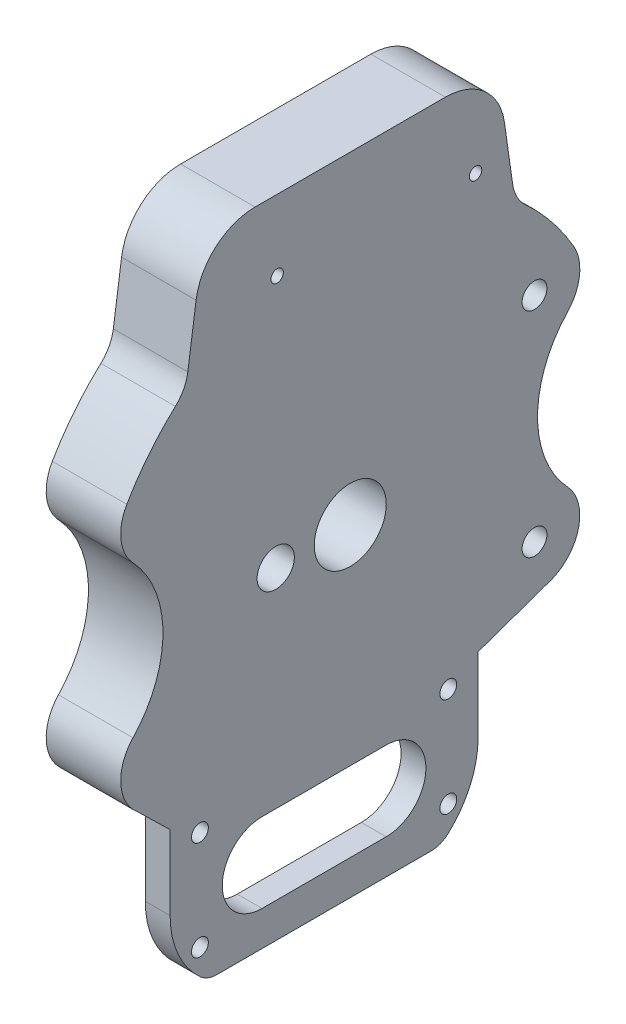
SolidWorks part; units mm, degrees
ref_plane "Płaszczyzna przednia" through (0, 0, 0) normal (0, 0, 1) x (1, 0, 0)
ref_plane "Płaszczyzna górna" through (0, 0, 0) normal (0, 1, 0) x (1, 0, 0)
ref_plane "Płaszczyzna prawa" through (0, 0, 0) normal (1, 0, 0) x (0, 0, -1)
sketch "Szkic1" plane through (0, 0, 0) normal (1, 0, 0) x (0, 0, -1)
  line L5 (0, 0) -> (0, 195.8303) construction
  line L42 (14.4695, -100) -> (-35.5305, -100) construction
  line L44 (14.4695, -84) -> (-35.5305, -84)
  line L45 (14.4695, -116) -> (-35.5305, -116)
  line L46 (30.5104, 100) -> (-9.4896, 100) construction
  line L47 (30.5104, 105) -> (-9.4896, 105) construction
  line L48 (30.5104, 95) -> (-9.4896, 95) construction
  line L49 (-10.5305, -100) -> (-10.5305, -46.7527) construction
  line L50 (-13.6636, -130) -> (20.5826, 195.8303) construction
  line L51 (0, 0) -> (120, 0) construction
  line L52 (0, 0) -> (0, -130.3815) construction
  line L53 (-72.5305, -70) -> (-85.8486, -57.0401)
  line L54 (-72.5305, -100) -> (-72.5305, -70)
  line L55 (51.4695, -70) -> (81.2407, -59.5241)
  line L56 (-35.5305, -130) -> (-53.6689, -130)
  line L57 (51.4695, -100) -> (51.4695, -70)
  line L58 (14.4695, -130) -> (32.6078, -130)
  line L59 (14.4695, -130) -> (-35.5305, -130)
  line L60 (62.0766, 109.386) -> (65.4007, 86.06)
  line L61 (-38.3166, 130) -> (38.3166, 130)
  line L62 (-62.0766, 109.386) -> (-65.4007, 86.06)
  circle A0 centre (0, 0) radius 14.5
  circle A3 centre (0, 0) radius 85.75 construction
  arc A56 (14.4695, -84) -> (14.4695, -116) centre (14.4695, -100) cw
  arc A57 (-35.5305, -116) -> (-35.5305, -84) centre (-35.5305, -100) cw
  arc A60 (30.5104, 105) -> (30.5104, 95) centre (30.5104, 100) cw construction
  arc A61 (-9.4896, 95) -> (-9.4896, 105) centre (-9.4896, 100) cw construction
  arc A62 (32.6078, -130) -> (39.3257, -127.4074) centre (32.6078, -120) ccw
  arc A63 (-60.3868, -127.4074) -> (-53.6689, -130) centre (-53.6689, -120) ccw
  arc A65 (51.4695, -100) -> (39.3257, -127.4074) centre (14.4695, -100) cw
  arc A66 (-60.3868, -127.4074) -> (-72.5305, -100) centre (-35.5305, -100) cw
  arc A67 (87.4958, -30.51) -> (81.2407, -59.5241) centre (74.4106, -42.8703) cw
  arc A68 (87.4958, -30.51) -> (87.4958, 30.51) centre (120, 0) cw
  arc A69 (89.9789, 52.1516) -> (87.4958, 30.51) centre (74.1894, 43) cw
  arc A70 (70.4086, 76.5417) -> (89.9789, 52.1516) centre (0, 0) cw
  arc A71 (65.4007, 86.06) -> (70.4086, 76.5417) centre (81.2407, 88.3174) ccw
  arc A72 (38.3166, 130) -> (62.0766, 109.386) centre (38.3166, 106) cw
  arc A73 (-38.3166, 130) -> (-62.0766, 109.386) centre (-38.3166, 106) ccw
  arc A74 (-65.4007, 86.06) -> (-70.4086, 76.5417) centre (-81.2407, 88.3174) cw
  arc A75 (-70.4086, 76.5417) -> (-89.9789, 52.1516) centre (0, 0) ccw
  arc A76 (-89.9789, 52.1516) -> (-87.4958, 30.51) centre (-74.1894, 43) ccw
  arc A77 (-87.4958, -30.51) -> (-87.4958, 30.51) centre (-120, 0) ccw
  arc A78 (-87.4958, -30.51) -> (-85.8486, -57.0401) centre (-74.1894, -43) ccw
  circle A79 centre (74.1894, -43) radius 5
  circle A80 centre (74.1894, 43) radius 5
  point P7 (-10.5305, -100)
  point P24 (-25, -70)
  point P25 (25, -70)
  point P30 (25, -100)
  point P31 (25, -130)
  point P33 (-25, -130)
  point P34 (-25, -100)
  point P41 (-25, -70)
  point P42 (25, -70)
  point P43 (-25.5104, 81)
  point P44 (25, -100)
  point P46 (-25, -130)
  point P47 (-25, -100)
  point P49 (62, -82.8995)
  point P58 (62, -100)
  point P59 (25, -100)
  point P60 (25, -137)
  point P61 (-25, -137)
  point P62 (-25, -100)
  point P63 (-62, -100)
  point P64 (-62, -82.8995)
  point P69 (10.5104, 100)
  point P72 (0, 126)
  point P192 (46.6564, -130)
  point P193 (-46.6564, -130)
  point P194 (74.1894, 43)
  point P195 (74.1894, -43)
  dimension "D1" = 29
  dimension "D7" = 171.5
extrude "Dodanie-wyciągnięcie1" add sketch "Szkic1" along normal mid plane 30
hole_wizard "Otwór gwintowany M61" positions "Sketch1" profile "Sketch2" tap size "M6" standard "ISO" end condition through all
sketch "Sketch1" plane through (-15, 0, 0) normal (1, 0, 0) x (0, 0, -1)
  line L0 (-81.5745, 104.2751) -> (63.3416, 96.6804) construction
  line L11 (0, 0) -> (0, 118.3984) construction
  line L12 (10.8009, 104.9924) -> (10.2776, 95.0061) construction
  point P50 (50.4556, 97.3557)
  point P51 (-29.4348, 101.5426)
  dimension "D1" = 93
  dimension "D2" = 40
  dimension "D3" = 40
sketch "Sketch2" plane through (-15, 101.5426, 29.4348) normal (0, 1, 0) x (0, 0, 1)
  line L0 (0, 0) -> (0, 30)
  line L1 (0, 30) -> (2.5, 30)
  line L2 (2.5, 30) -> (2.5, 0)
  line L5 (2.5, 0) -> (0, 0)
  line L11 (0, -6.35) -> (0, 107.95) construction
  dimension "Thru Tap Drill Dia." = 5
  dimension "Thru Tap Drill Depth" = 30
cosmetic thread "Gwint otworu5" parameters "D2"=6
cosmetic thread "Gwint otworu6" parameters "D2"=6
sketch "Szkic12" plane through (-15, 0, 0) normal (1, 0, 0) x (0, 0, -1)
  line L0 (0, 0) -> (0, 198.2502) construction
  line L1 (50.4556, 97.3557) -> (-29.4348, 101.5426) construction
  line L2 (28.8022, 93.4837) -> (-9.7329, 95.5032)
  line L3 (-9.2095, 105.4895) -> (29.3255, 103.47)
  arc A0 (-9.7329, 95.5032) -> (-9.2095, 105.4895) centre (-9.4712, 100.4964) cw
  arc A1 (29.3255, 103.47) -> (28.8022, 93.4837) centre (29.0639, 98.4768) cw
  circle A2 centre (-29.4348, 101.5426) radius 2.5 construction
  circle A3 centre (50.4556, 97.3557) radius 2.5 construction
  circle A4 centre (-29.4348, 101.5426) radius 2.5
  circle A5 centre (50.4556, 97.3557) radius 2.5
  dimension "D3" = 5
  dimension "D1" = 93
  dimension "D2" = 10
extrude "Wytnij-wyciągnięcie2" cut sketch "Szkic12" along normal blind 10 contours A0 L3 A1 L2
sketch "Szkic16" plane through (-15, 0, 0) normal (1, 0, 0) x (0, 0, -1)
  line L5 (-35.5305, -116) -> (14.4695, -116)
  line L6 (14.4695, -84) -> (-35.5305, -84)
  line L8 (-53.6689, -130) -> (32.6078, -130)
  line L10 (-83.0611, -100) -> (40.9389, -100) construction
  line L11 (-72.5305, -70) -> (51.4695, -70)
  line L13 (-72.5305, -70) -> (-72.5305, -100)
  line L16 (51.4695, -70) -> (51.4695, -100)
  arc A6 (-35.5305, -84) -> (-35.5305, -116) centre (-35.5305, -100) ccw
  arc A7 (14.4695, -116) -> (14.4695, -84) centre (14.4695, -100) ccw
  arc A9 (32.6078, -130) -> (39.3257, -127.4074) centre (32.6078, -120) ccw
  arc A10 (-60.3868, -127.4074) -> (-53.6689, -130) centre (-53.6689, -120) ccw
  arc A20 (39.3257, -127.4074) -> (51.4695, -100) centre (14.4695, -100) ccw
  arc A21 (-72.5305, -100) -> (-60.3868, -127.4074) centre (-35.5305, -100) ccw
extrude "Wytnij-wyciągnięcie4" cut sketch "Szkic16" along normal blind 20
chamfer "Sfazowanie4" distance 10 angle 45 1 edges at (-15, -70, 10.5305)
sketch "Szkic17" plane through (-15, 0, 0) normal (1, 0, 0) x (0, 0, -1)
  line L2 (0, 0) -> (0, 36.4505) construction
  line L3 (-45.2929, 8.9572) -> (-31.5786, 10.9367)
  line L6 (-31.5786, -10.9367) -> (-45.2929, -8.9572)
  arc A7 (-45.2929, -8.9572) -> (-45.2929, 8.9572) centre (-44, 0) cw
  circle A8 centre (-30, 0) radius 7.5
  arc A10 (-18.9801, -0.8154) -> (-31.5786, -10.9367) centre (-30, 0) cw
  arc A12 (-31.5786, 10.9367) -> (-18.9801, -0.8154) centre (-30, 0) cw
  point P0 (8.9572, 38.7071)
  point P1 (-0.6678, 49.0253)
  point P2 (30, 0)
  point P3 (-8.9572, 38.7071)
  point P5 (-6.9777, 24.9929)
  point P6 (0, 26)
  point P7 (4.5988, 31.3435)
  point P8 (0, 26)
  point P9 (6.9777, 24.9929)
  point P20 (45.2929, -8.9572)
  point P21 (0, 26)
  point P22 (5.9035, 32.8594)
  point P23 (44, 0)
  point P24 (45.2929, 8.9572)
extrude "Wytnij-wyciągnięcie5" cut sketch "Szkic17" along normal blind 5 contours A8 | A7 L3 A12 A10 L6
extrude "Wytnij-wyciągnięcie6" cut sketch "Szkic17<5>" along normal through all contours A8
sketch "Szkic17<5>" plane through (-15, 0, 0) normal (1, 0, 0) x (0, 0, -1) same geometry as "Szkic17"
sketch "Szkic18" plane through (5, 0, 0) normal (-1, 0, 0) x (0, 0, 1)
  line L0 (10.5305, -84) -> (10.5305, -116) construction
  line L3 (-30.4695, -100) -> (51.5305, -100) construction
  point P14 (-39.4695, -77)
  point P17 (60.5305, -77)
  point P18 (60.5305, -117)
  point P19 (-39.4695, -117)
  dimension "D1" = 23
  dimension "D2" = 50
  dimension "D3" = 2
  dimension "D4" = 2
hole_wizard "Otwór gwintowany M81" positions "Szkic 3D1" profile "Szkic19" tap size "M8" standard "ISO"
sketch3d "Szkic 3D1"
  point P0 (5, -77, -39.4695)
  point P3 (5, -117, -39.4695)
  point P6 (5, -117, 60.5305)
  point P9 (5, -77, 60.5305)
sketch "Szkic19" plane through (5, -77, -39.4695) normal (0, 1, 0) x (0, 0, 1)
  line L0 (0, 0) -> (0, 18.25)
  line L1 (0, 18.25) -> (3.4, 16.2071)
  line L2 (3.4, 16.2071) -> (3.4, 0.625)
  line L3 (3.4, 0.625) -> (4.025, 0)
  line L5 (4.025, 0) -> (0, 0)
  line L6 (-3.4, 0.625) -> (-4.025, 0) construction
  line L10 (0, 18.25) -> (-3.4, 16.2071) construction
  line L11 (0, -6.35) -> (0, 107.95) construction
  dimension "Średnica wiertła gwintu" = 6.8
  dimension "Głębokość otworu gwintowanego" = 18.25
  dimension "Średnica zewnętrznego pogłębienia stożkowego" = 8.05
  dimension "Kąt zewnętrznego pogłębienia stożkowego" = 90
  dimension "Kąt wiertła" = 118
cosmetic thread "Gwint otworu1" parameters "D1"=10, "D2"=8
cosmetic thread "Gwint otworu2" parameters "D1"=10, "D2"=8
cosmetic thread "Gwint otworu3" parameters "D1"=10, "D2"=8
cosmetic thread "Gwint otworu4" parameters "D1"=10, "D2"=8
